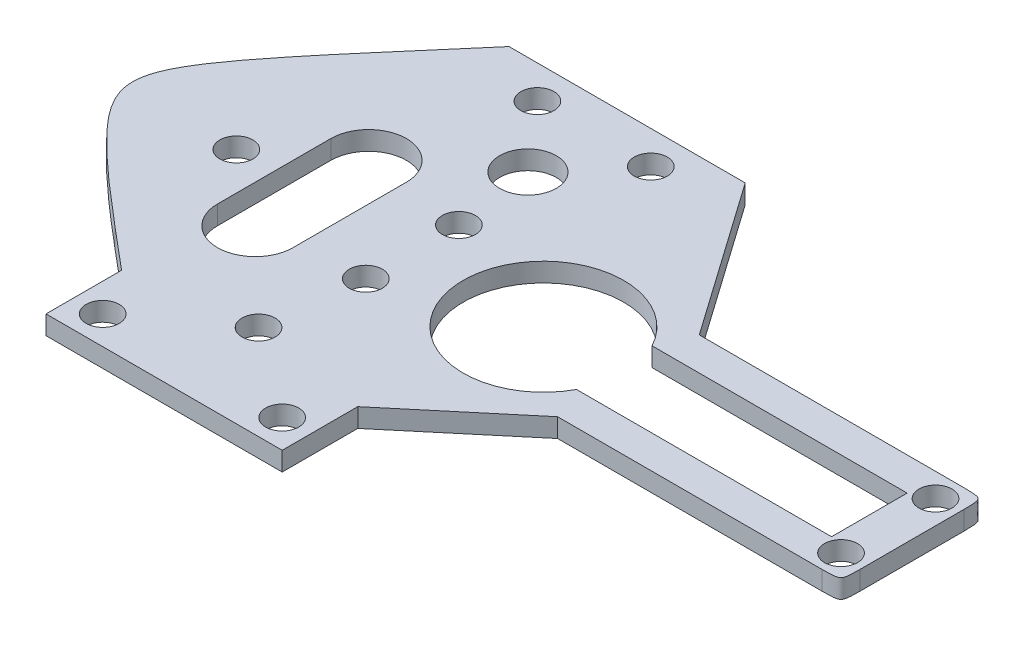
SolidWorks part; units mm, degrees
material "1023 Carbon Steel Sheet (SS)"
ref_plane "Front Plane" through (0, 0, 0) normal (0, 0, 1) x (1, 0, 0)
ref_plane "Top Plane" through (0, 0, 0) normal (0, 1, 0) x (1, 0, 0)
ref_plane "Right Plane" through (0, 0, 0) normal (1, 0, 0) x (0, 0, -1)
sketch "Sketch1" plane through (0, 0, 0) normal (0, 1, 0) x (1, 0, 0)
  line L5 (12.5, -17.1496) -> (24, -7.5)
  line L6 (24, -7.5) -> (54, -7.5)
  line L7 (54, -7.5) -> (54, 7.5)
  line L8 (54, 7.5) -> (24, 7.5)
  line L9 (24, 7.5) -> (12.5, 23.8631)
  line L13 (-12.5, 23.8631) -> (-32.9382, 0)
  line L15 (-32.9382, 0) -> (-12.5, -17.1496)
  line L16 (15, 0) -> (34.9396, 0) construction
  line L17 (22.5, 4) -> (49.5, 4)
  line L19 (22.5, -4) -> (49.5, -4)
  line L20 (49.5, 4) -> (49.5, -4)
  line L23 (-12.5, -17.1496) -> (-12.5, -25.1496)
  line L24 (-12.5, -25.1496) -> (12.5, -25.1496)
  line L25 (12.5, -17.1496) -> (12.5, -25.1496)
  line L26 (-12.5, 23.8631) -> (12.5, 23.8631)
  arc A0 (22.5, 4) -> (22.5, -4) centre (15, 0) ccw
  circle A1 centre (51.5, -5) radius 1.75
  circle A2 centre (51.5, 5) radius 1.75
  point P1 (0, -25.1496)
  point P3 (0, 23.8631)
  dimension "D17" = 17
  dimension "D18" = 9
  dimension "D22" = 3.5
  dimension "D10" = 15
  dimension "D3" = 8
  dimension "D4" = 130
  dimension "D5" = 30
  dimension "D6" = 130
  dimension "D7" = 20
  dimension "D8" = 25
  dimension "D9" = 25
  dimension "D12" = 7.5
  dimension "D13" = 15
  dimension "D19" = 7.5
  dimension "D20" = 8
  dimension "D21" = 27
  dimension "D23" = 2.5
  dimension "D24" = 2.5
extrude "Boss-Extrude1" add sketch "Sketch1" along normal blind 2
fillet "Fillet2" radius 21 1 edges at (-32.9382, 1, 0) conic rho 0.75
fillet "Fillet3" radius 2 2 edges at (54, 1, -7.5) (54, 1, 7.5) conic rho 0.75
sketch "Sketch2" plane through (0, 2, 0) normal (0, 1, 0) x (1, 0, 0)
  line L1 (0, 23.8631) -> (0, 13.3631) construction
  line L4 (0, -25.1496) -> (0, -4) construction
  line L6 (-12.5, -25.1496) -> (12.5, -25.1496) construction
  line L7 (-9.5, 6) -> (-9.5, -6) construction
  line L8 (-5.5, 6) -> (-5.5, -6)
  line L9 (-13.5, 6) -> (-13.5, -6)
  line L10 (12.5, -25.1496) -> (12.5, -17.1496) construction
  line L11 (12.5, 23.8631) -> (-12.5, 23.8631) construction
  circle A0 centre (-9.5, -22.1496) radius 1.75
  circle A1 centre (9.5, -22.1496) radius 1.75
  circle A2 centre (6, 20.3631) radius 1.75
  circle A3 centre (-6, 20.3631) radius 1.75
  circle A4 centre (0, -15.1496) radius 1.75
  circle A5 centre (-17.5, 0) radius 1.75
  arc A6 (-5.5, 6) -> (-13.5, 6) centre (-9.5, 6) ccw
  arc A7 (-13.5, -6) -> (-5.5, -6) centre (-9.5, -6) ccw
  circle A8 centre (1.2002, 4.8538) radius 1.75
  circle A9 centre (0, 13.3631) radius 3
  circle A10 centre (1.2, -5) radius 1.75
  circle A11 centre (51.5, -5) radius 1.75 construction
  circle A12 centre (51.5, 5) radius 1.75 construction
  point P23 (-9.5, 0)
  dimension "D1" = 3.5
  dimension "D4" = 3.5
  dimension "D7" = 3.5
  dimension "D9" = 3.5
  dimension "D13" = 6
  dimension "D16" = 3.5
  dimension "D17" = 3.5
  dimension "D19" = 7
  dimension "D2" = 3
  dimension "D3" = 3
  dimension "D5" = 10
  dimension "D6" = 8
  dimension "D8" = 6
  dimension "D10" = 5
  dimension "D11" = 12
  dimension "D12" = 8
  dimension "D14" = 3.5
  dimension "D15" = 5
  dimension "D18" = 5
  dimension "D20" = 50.3
  dimension "50.5" = 50.3
extrude "Cut-Extrude1" cut sketch "Sketch2" against normal through all
